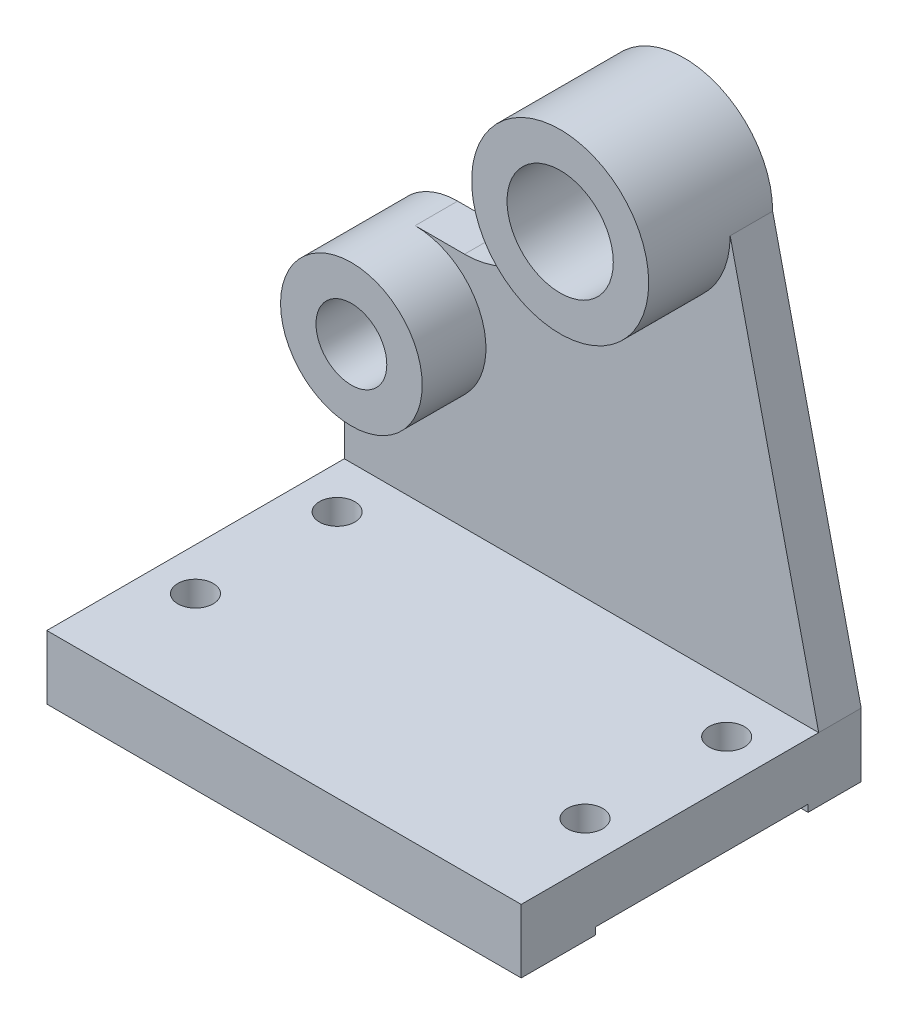
SolidWorks part; units mm, degrees
ref_plane "Front Plane" through (0, 0, 0) normal (0, 0, 1) x (1, 0, 0)
ref_plane "Top Plane" through (0, 0, 0) normal (0, 1, 0) x (1, 0, 0)
ref_plane "Right Plane" through (0, 0, 0) normal (1, 0, 0) x (0, 0, -1)
sketch "Sketch1" plane through (0, 0, 0) normal (0, 0, 1) x (1, 0, 0)
  line L0 (66.9757, 9) -> (41.9757, 118)
  line L1 (-66.9757, 9) -> (66.9757, 9)
  line L2 (-66.9757, 9) -> (-66.9757, -9)
  line L3 (-66.9757, -9) -> (66.9757, -9)
  line L4 (66.9757, 9) -> (66.9757, -9)
  line L5 (-66.9757, 9) -> (66.9757, -9) construction
  line L6 (-66.9757, -9) -> (66.9757, 9) construction
  line L7 (-46.9757, 76) -> (-33.0243, 76)
  line L8 (-8.0243, 118) -> (-8.0243, 101)
  line L9 (-66.9757, 56) -> (-66.9757, 9)
  circle A0 centre (-46.9757, 56) radius 10
  circle A1 centre (-46.9757, 56) radius 20
  circle A2 centre (16.9757, 118) radius 15
  circle A3 centre (16.9757, 118) radius 25
  arc A4 (-33.0243, 76) -> (-8.0243, 101) centre (-33.0243, 101) ccw
  point P0 (0, 0)
  point P9 (-66.9757, 0)
  point P13 (66.9757, 0)
  dimension "D3" = 20
  dimension "D5" = 50
  dimension "D7" = 25
  dimension "D1" = 133.9514
  dimension "D2" = 18
  dimension "D4" = 56
  dimension "D6" = 118
extrude "Boss-Extrude1" add sketch "Sketch1" along normal blind 96 contours L4 L1 L2 L3 region at (0, 0, 0)
extrude "Boss-Extrude2" add sketch "Sketch1<3>" along normal blind 12 contours A4 L7 A1 L9 L1 L0 A3 L8 region at (6.8658, 47.2118, 0)
sketch "Sketch1<3>" plane through (0, 0, 0) normal (0, 0, 1) x (1, 0, 0) same geometry as "Sketch1"
extrude "Boss-Extrude3" add sketch "Sketch1<4>" along normal blind 30 contours A1 A0 region at (-60.7178, 69.7421, 0)
sketch "Sketch1<4>" plane through (0, 0, 0) normal (0, 0, 1) x (1, 0, 0) same geometry as "Sketch1"
extrude "Boss-Extrude4" add sketch "Sketch1<5>" along normal blind 35 contours A3 A2 region at (16.9757, 93.7071, 0)
sketch "Sketch1<5>" plane through (0, 0, 0) normal (0, 0, 1) x (1, 0, 0) same geometry as "Sketch1"
sketch "Sketch2" plane through (66.9757, 0, 0) normal (1, 0, 0) x (0, 0, -1)
  line L0 (-81.3444, 9) -> (-81.3444, -9) construction
  line L1 (-96, 9) -> (-12, 9) construction
  line L2 (-96, -9) -> (0, -9) construction
  line L4 (0, -9) -> (-15, -9)
  line L5 (-15, -9) -> (-15, -7)
  line L6 (-15, -7) -> (-75, -7)
  line L7 (-75, -7) -> (-75, -9)
  line M8 (-96, -9) -> (0, -9)
  dimension "D1" = 15
  dimension "D2" = 60
extrude "Cut-Extrude1" cut sketch "Sketch2" against normal blind 140 and the other way through all contours L6 L7 L5 M8 region at (66.9757, -8, 45)
sketch "Sketch4" plane through (0, 9, 0) normal (0, 1, 0) x (1, 0, 0)
  circle A0 centre (55, -26) radius 5
  circle A1 centre (55, -66) radius 5
  circle A2 centre (-55, -66) radius 5
  circle A3 centre (-55, -26) radius 5
extrude "Cut-Extrude3" cut sketch "Sketch4" against normal blind 35 contours A0 | A1 | A2
sketch "Sketch5" plane through (0, 9, 0) normal (0, 1, 0) x (1, 0, 0)
  circle A0 centre (-55, -26) radius 5
extrude "Cut-Extrude4" cut sketch "Sketch5" against normal blind 35
